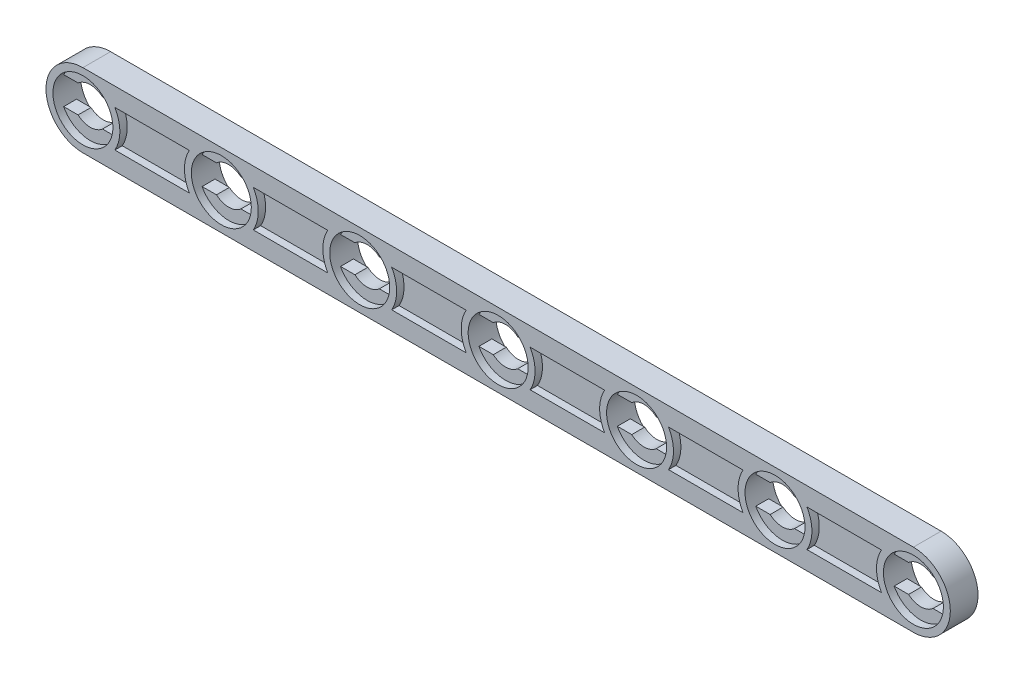
SolidWorks part; units mm, degrees
ref_plane "前视基准面" through (0, 0, 0) normal (0, 0, 1) x (1, 0, 0)
ref_plane "上视基准面" through (0, 0, 0) normal (0, 1, 0) x (1, 0, 0)
ref_plane "右视基准面" through (0, 0, 0) normal (1, 0, 0) x (0, 0, -1)
sketch "草图1" plane through (0, 0, 0) normal (0, 0, 1) x (1, 0, 0)
  line L1 (0, 4) -> (90, 4)
  line L3 (0, -4) -> (90, -4)
  arc A0 (0, 4) -> (0, -4) centre (0, 0) ccw
  arc A1 (90, -4) -> (90, 4) centre (90, 0) ccw
  dimension "D1" = 4
  dimension "D2" = 90
  dimension "D3" = 90
extrude "凸台-拉伸1" add sketch "草图1" against normal blind 3
sketch "草图2" plane through (0, 0, 0) normal (0, 0, 1) x (1, 0, 0)
  line L0 (1.3229, -1.5) -> (2.8831, -1.5)
  line L1 (-2.8831, -1.5) -> (-1.3229, -1.5)
  line L2 (1.3229, 1.5) -> (2.8831, 1.5)
  line L3 (-2.8831, 1.5) -> (-1.3229, 1.5)
  arc A0 (1.3229, 1.5) -> (-1.3229, 1.5) centre (0, 0) ccw
  arc A1 (-2.8831, 1.5) -> (-2.8831, -1.5) centre (0, 0) ccw
  arc A3 (2.8831, -1.5) -> (2.8831, 1.5) centre (0, 0) ccw
  arc A4 (-1.3229, -1.5) -> (1.3229, -1.5) centre (0, 0) ccw
extrude "切除-拉伸1" cut sketch "草图2" against normal up to next
sketch "草图3" plane through (0, 0, 0) normal (0, 0, 1) x (1, 0, 0)
  circle A1 centre (0, 0) radius 3.25
extrude "切除-拉伸2" cut sketch "草图3" against normal blind 0.8
extrude "切除-拉伸3" cut sketch "草图3<2>" along normal blind 0.8 from offset 3 offset against normal yes
sketch "草图3<2>" plane through (0, 0, 0) normal (0, 0, 1) x (1, 0, 0) same geometry as "草图3"
sketch "草图4" plane through (0, 0, 0) normal (0, 0, 1) x (1, 0, 0)
  line L1 (3.4641, 2) -> (11.5359, 2)
  line L3 (3.4641, -2) -> (11.5359, -2)
  arc A0 (11.5359, 2) -> (11.5359, -2) centre (15, 0) ccw
  arc A2 (3.4641, -2) -> (3.4641, 2) centre (0, 0) ccw
extrude "切除-拉伸4" cut sketch "草图4" against normal blind 0.8
sketch "草图5" plane through (0, 0, -3) normal (0, 0, -1) x (-1, 0, 0)
  line L1 (-4, -2) -> (-11, -2)
  line L2 (-4, -2) -> (-4, 2)
  line L3 (-4, 2) -> (-11, 2)
  line L4 (-11, -2) -> (-11, 2)
extrude "切除-拉伸6" cut sketch "草图5" against normal blind 0.8
pattern_linear "阵列(线性)1" count 7 spacing 15 along (1, 0, 0) of "切除-拉伸1", "切除-拉伸2", "切除-拉伸3"
pattern_linear "阵列(线性)2" count 6 spacing 15 along (1, 0, 0) of "切除-拉伸4", "切除-拉伸6"
